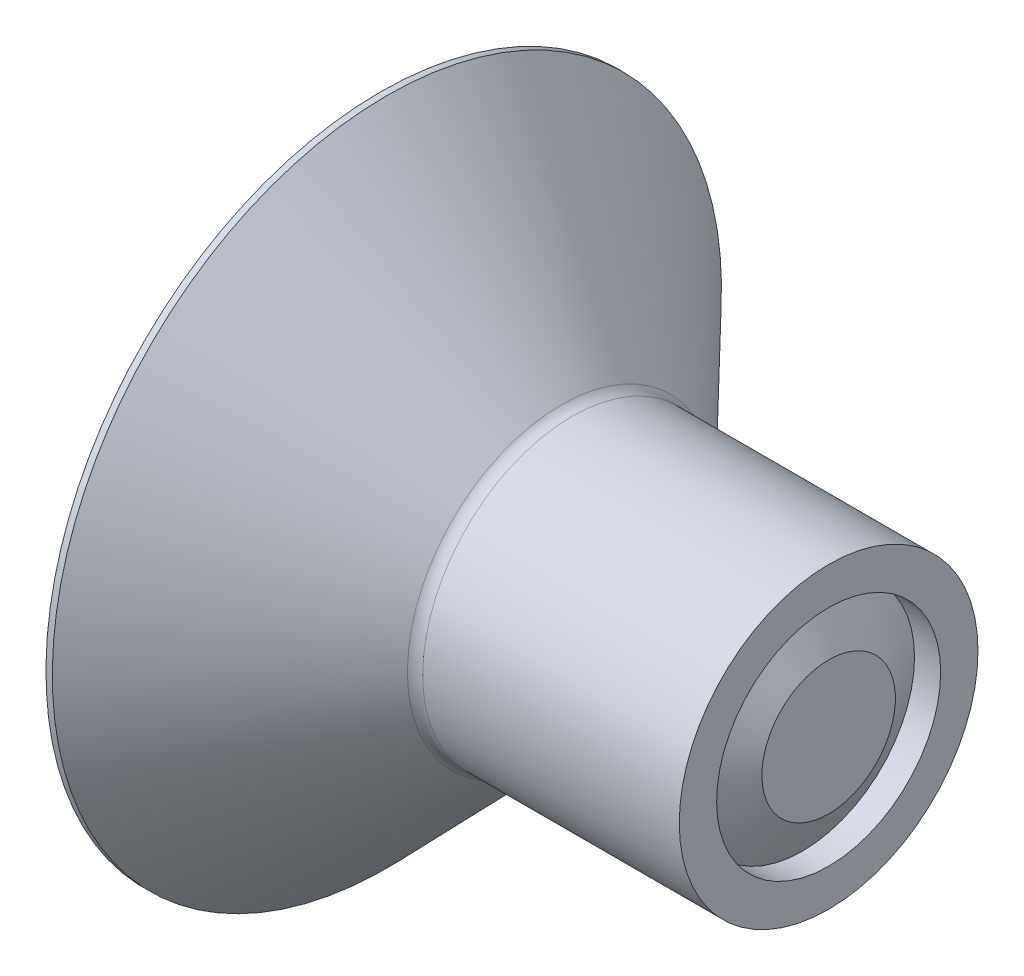
SolidWorks part; units mm, degrees
material "8.8级"
ref_plane "前视基准面" through (0, 0, 0) normal (0, 0, 1) x (1, 0, 0)
ref_plane "上视基准面" through (0, 0, 0) normal (0, 1, 0) x (1, 0, 0)
ref_plane "右视基准面" through (0, 0, 0) normal (1, 0, 0) x (0, 0, -1)
sketch "草图1" plane through (0, 0, 0) normal (0, 0, 1) x (1, 0, 0)
  line L0 (0, 2) -> (-3.4351, 2)
  line L1 (-3.579, 2.0611) -> (-5.9149, 4.48)
  line L2 (-5.9149, 4.48) -> (-6, 4.48)
  line L3 (-6, 4.48) -> (-6, 0)
  line L4 (-6, 0) -> (0, 0)
  line L5 (0, 0) -> (0, 2)
  line L6 (0, 0) -> (-6, 0) construction
  arc A0 (-3.4351, 2) -> (-3.579, 2.0611) centre (-3.4351, 2.2) cw
  point P9 (-3.52, 2)
  dimension "r" = 0.2
  dimension "k" = 2.48
  dimension "dk" = 8.96
  dimension "l" = 6
  dimension "D5" = 46
  dimension "d" = 4
revolve "旋转1" add sketch "草图1" angle 360 about L6
cosmetic thread "装饰螺纹线1" parameters "b"=6, "D2"=2.58
sketch "草图2" plane through (-6, 0, 0) normal (-1, 0, 0) x (0, 0, 1)
  line L1 (0, 1.4434) -> (-1.25, 0.7217)
  line L2 (-1.25, 0.7217) -> (-1.25, -0.7217)
  line L3 (-1.25, -0.7217) -> (0, -1.4434)
  line L4 (0, -1.4434) -> (1.25, -0.7217)
  line L5 (1.25, -0.7217) -> (1.25, 0.7217)
  line L6 (1.25, 0.7217) -> (0, 1.4434)
  circle A0 centre (0, 0) radius 1.25 construction
  dimension "s" = 2.5
extrude "切除-拉伸1" cut sketch "草图2" against normal blind 1.96
sketch "草图6" plane through (0, 0, 0) normal (0, 0, 1) x (1, 0, 0)
  line L0 (-4.5, 1.4434) -> (-3.6667, 0)
  line L1 (-3.6667, 0) -> (-3.74, 0)
  line L2 (-3.74, 0) -> (-3.74, 1.4434)
  line L3 (-3.74, 1.4434) -> (-4.5, 1.4434)
  line L4 (-6, 0) -> (-4.04, 0) construction
  line L5 (-6, 0) -> (-8.87, 0) construction
  dimension "D1" = 60
  dimension "t" = 1.5
  dimension "t1" = 1.96
  dimension "e-s" = 0.3
  dimension "e" = 2.87
revolve "旋转2" add sketch "草图6" angle 360 about L4 rebuild error yes
sketch "草图7" plane through (0, 0, 0) normal (0, 0, 1) x (1, 0, 0)
  line L0 (-6, 1.4434) -> (-6, 0)
  line L1 (-6, 0) -> (-5.67, 0)
  line L2 (-5.67, 0) -> (-6, 1.4434)
  line L3 (-6, 0) -> (-5.67, 0) construction
  dimension "e-s*1.1" = 0.33
revolve "切除-旋转2" cut sketch "草图7" angle 360 about L3
sketch "草图4" plane through (0, 0, 0) normal (0, 0, 1) x (1, 0, 0)
  line L0 (-0.35, 1.5) -> (0, 0.8938)
  line L1 (0, -2) -> (0, 2) construction
  line L2 (0, 0.8938) -> (0.35, 1.5)
  line L3 (0.35, 1.5) -> (-0.35, 1.5)
  line L4 (-0.35, 0) -> (0.35, 0) construction
  dimension "d" = 3
  dimension "p" = 0.7
revolve "切除-旋转1" cut sketch "草图4" angle 360 about L4
ref_axis "基准轴1" through (-21.1715, 0, 0) along (1, 0, 0)
pattern_linear "阵列(线性)2" [suppressed] count 28 spacing 0.5 along (-1, 0, 0) of bodies 104
equation "\"D2@装饰螺纹线1\" = \"d@草图1\" * 0.86"
equation "\"e-s@草图6\" = \"e@草图6\" - \"s@草图2\""
equation "\"t1@切除-拉伸1\" = \"k@草图1\" + 0.1"
equation "\"t1@草图6\" = \"t1@切除-拉伸1\""
equation "\"e-s*1.1@草图7\" = \"e-s@草图6\" * 1.1"
equation "\"d@草图4\" = \"d@草图1\""
equation "\"D3@阵列(线性)2\" = \"p@草图4\""
equation "\"D1@阵列(线性)2\" = \"b@装饰螺纹线1\" / \"p@草图4\""
